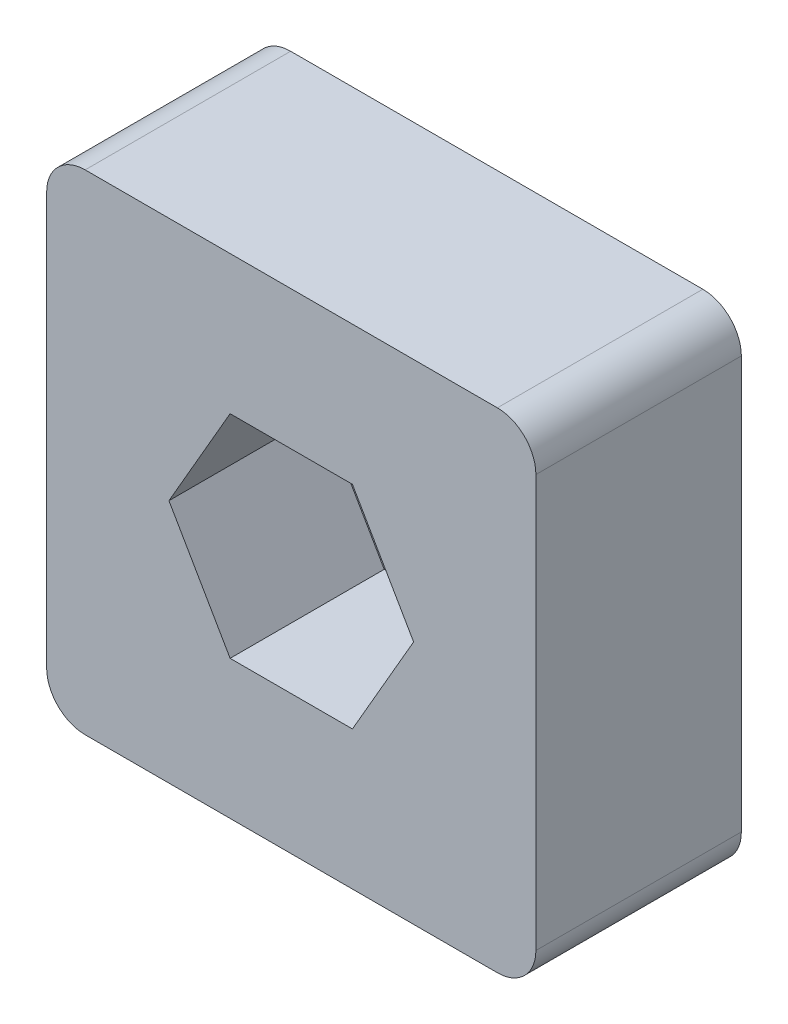
SolidWorks part; units mm, degrees
ref_plane "Front Plane" through (0, 0, 0) normal (0, 0, 1) x (1, 0, 0)
ref_plane "Top Plane" through (0, 0, 0) normal (0, 1, 0) x (1, 0, 0)
ref_plane "Right Plane" through (0, 0, 0) normal (1, 0, 0) x (0, 0, -1)
sketch "Sketch1" plane through (0, 0, 0) normal (0, 0, 1) x (1, 0, 0)
  line L1 (0, 0) -> (19.05, 0)
  line L2 (0, 0) -> (0, 19.05)
  line L3 (0, 19.05) -> (19.05, 19.05)
  line L4 (19.05, 0) -> (19.05, 19.05)
  dimension "D1" = 19.05
  dimension "D2" = 19.05
extrude "Boss-Extrude1" add sketch "Sketch1" along normal blind 8
sketch "Sketch2" plane through (0, 0, 8) normal (0, 0, 1) x (1, 0, 0)
  line L0 (0, 9.525) -> (19.05, 9.525) construction
  line L1 (0, 19.05) -> (0, 0) construction
  line L2 (19.05, 0) -> (19.05, 19.05) construction
  line L4 (14.2881, 9.525) -> (11.9066, 13.65)
  line L5 (11.9066, 13.65) -> (7.1434, 13.65)
  line L6 (7.1434, 13.65) -> (4.7619, 9.525)
  line L7 (4.7619, 9.525) -> (7.1434, 5.4)
  line L8 (7.1434, 5.4) -> (11.9066, 5.4)
  line L9 (11.9066, 5.4) -> (14.2881, 9.525)
  circle A0 centre (9.525, 9.525) radius 4.125 construction
  circle A1 centre (9.525, 9.525) radius 2.75
  point P15 (0, 0)
  dimension "D2" = 5.5
  dimension "D1" = 8.25
extrude "Cut-Extrude1" cut sketch "Sketch2" against normal offset from surface (6 mm away) 2 contours A1 | L8 L9 L4 L5 L6 L7 A1 region at (12.9882, 7.5255, 8) region at (9.525, 9.525, 8) up to face at (9.525, 9.525, 0)
extrude "Cut-Extrude2" cut sketch "Sketch2<3>" against normal through all both and the other way through all contours A1 region at (9.525, 9.525, 8)
sketch "Sketch2<3>" plane through (0, 0, 8) normal (0, 0, 1) x (1, 0, 0) same geometry as "Sketch2"
fillet "Fillet1" radius 1.5 4 edges at (19.05, 0, 4) (0, 0, 4) (19.05, 19.05, 4) (0, 19.05, 4)
